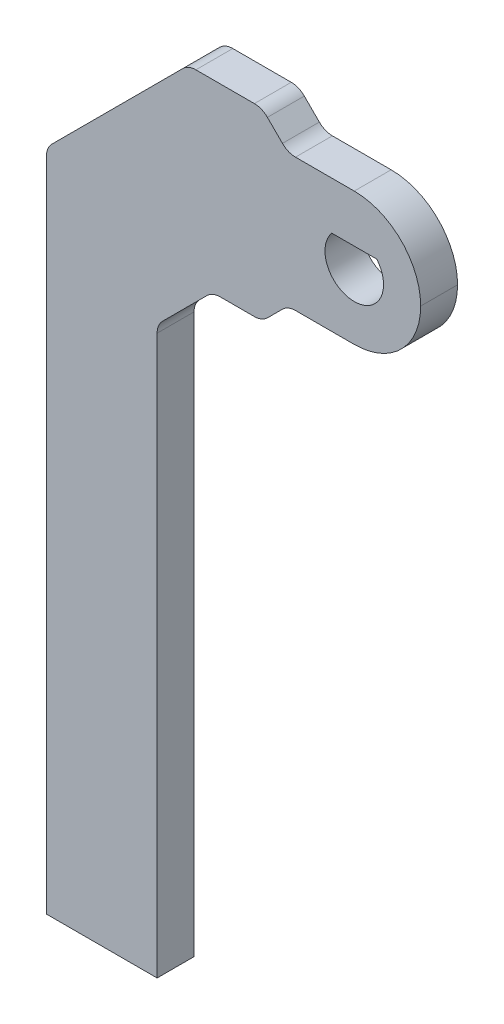
SolidWorks part; units mm, degrees
ref_plane "Plan de face" through (0, 0, 0) normal (0, 0, 1) x (1, 0, 0)
ref_plane "Plan de dessus" through (0, 0, 0) normal (0, 1, 0) x (1, 0, 0)
ref_plane "Plan de droite" through (0, 0, 0) normal (1, 0, 0) x (0, 0, -1)
sketch "Esquisse2" plane through (0, 0, 0) normal (0, 0, 1) x (1, 0, 0)
  line L0 (0, 0) -> (0, 90)
  line L1 (0, 90) -> (19.2157, 109.2157)
  line L2 (19.2157, 109.2157) -> (29.2157, 109.2157)
  line L4 (29.2157, 84.2157) -> (22.5, 84.2157)
  line L5 (22.5, 84.2157) -> (15, 76.7157)
  line L6 (15, 76.7157) -> (15, 0)
  line L11 (29.2157, 84.2157) -> (32.7157, 87.7157)
  line L12 (32.7157, 87.7157) -> (50.7157, 87.7157)
  line L13 (50.7157, 87.7157) -> (50.7157, 105.7157)
  line L14 (50.7157, 105.7157) -> (32.7157, 105.7157)
  line L15 (32.7157, 105.7157) -> (29.2157, 109.2157)
  line L16 (32.7157, 87.7157) -> (32.7157, 105.7157) construction
  line L17 (15, 0) -> (0, 0)
  circle A2 centre (41.7157, 96.7157) radius 3.9687
  dimension "D8" = 135
  dimension "D9" = 135
  dimension "D11" = 18
  dimension "D12" = 25
  dimension "D15" = 9
  dimension "D13" = 7.9375
  dimension "D2" = 10
  dimension "D3" = 45
  dimension "D4" = 20
  dimension "D5" = 7.5
  dimension "D6" = 15
  dimension "D7" = 90
  dimension "D10" = 3.5
  dimension "D14" = 9
extrude "Boss.-Extru.6" add sketch "Esquisse2" along normal blind 5
sketch "Esquisse3" plane through (0, 0, 5) normal (0, 0, 1) x (1, 0, 0)
  line L0 (38.6662, 99.2557) -> (44.7652, 99.2557)
  circle A0 centre (41.7157, 96.7157) radius 3.9687 construction
  arc A1 (38.6662, 99.2557) -> (44.7652, 99.2557) centre (41.7157, 96.7157) cw
  dimension "D1" = 2.54
extrude "Boss.-Extru.7" add sketch "Esquisse3" against normal through all
fillet "Congé1" radius 9 2 edges at (50.7157, 87.7157, 2.5) (50.7157, 105.7157, 2.5)
fillet "Congé2" radius 2.5 8 edges at (15, 76.7157, 2.5) (22.5, 84.2157, 2.5) (29.2157, 84.2157, 2.5) (32.7157, 87.7157, 2.5) (0, 90, 2.5) (19.2157, 109.2157, 2.5) (29.2157, 109.2157, 2.5) (32.7157, 105.7157, 2.5)
